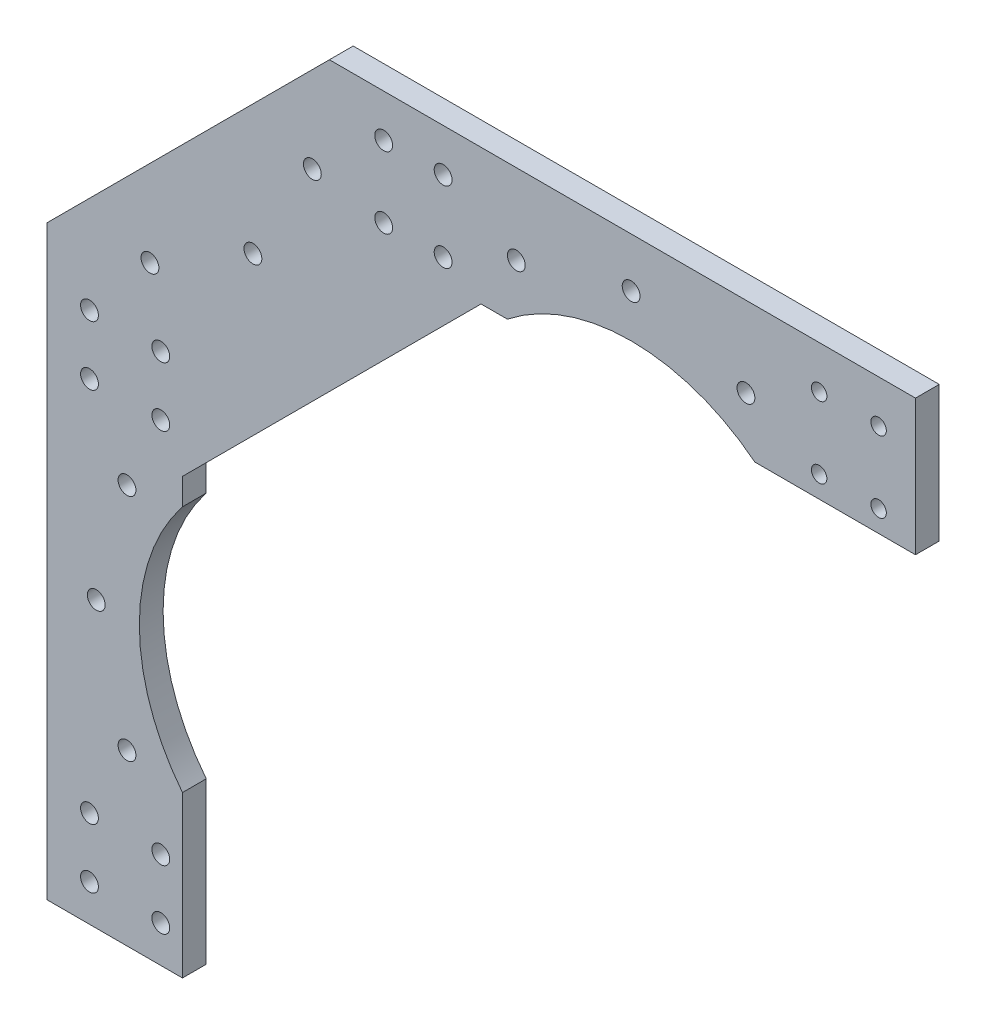
SolidWorks part; units mm, degrees
ref_plane "Front Plane" through (0, 0, 0) normal (0, 0, 1) x (1, 0, 0)
ref_plane "Top Plane" through (0, 0, 0) normal (0, 1, 0) x (1, 0, 0)
ref_plane "Right Plane" through (0, 0, 0) normal (1, 0, 0) x (0, 0, -1)
sketch "Sketch1" plane through (0, 0, 0) normal (0, 0, 1) x (1, 0, 0)
  line L0 (0, 0) -> (0, 75.4924) construction
  line L1 (-98.3263, -47.8405) -> (-75.4924, -47.8405)
  line L2 (-98.3263, -47.8405) -> (-98.3263, 50.769)
  line L4 (-75.4924, -47.8405) -> (-75.4924, 25.2528) construction
  line L5 (-50.769, 98.3263) -> (47.8405, 98.3263)
  line L7 (-25.2528, 75.4924) -> (47.8405, 75.4924) construction
  line L8 (47.8405, 98.3263) -> (47.8405, 75.4924)
  line L9 (0, 0) -> (-75.4924, 0) construction
  line L10 (-25.2528, 75.4924) -> (-75.4924, 25.2528)
  line L11 (-75.4924, 75.4924) -> (-25.2528, 75.4924) construction
  line L12 (-75.4924, 25.2528) -> (-75.4924, 75.4924) construction
  line L13 (-50.769, 98.3263) -> (-98.3263, 50.769)
  line L14 (-98.3263, 98.3263) -> (-50.769, 98.3263) construction
  line L15 (-98.3263, 50.769) -> (-98.3263, 98.3263) construction
  line L16 (-20.8161, 75.4924) -> (-25.2528, 75.4924)
  line L17 (20.8161, 75.4924) -> (47.8405, 75.4924)
  line L18 (-75.4924, 25.2528) -> (-75.4924, 20.8161)
  line L19 (-75.4924, -47.8405) -> (-75.4924, -20.8161)
  line L20 (-75.4924, 20.8161) -> (-75.4924, -20.8161) construction
  line L21 (-20.8161, 75.4924) -> (20.8161, 75.4924) construction
  arc A0 (20.8161, 75.4924) -> (-20.8161, 75.4924) centre (0, 49.2714) ccw
  arc A1 (-75.4924, 20.8161) -> (-75.4924, -20.8161) centre (-49.2714, 0) ccw
  dimension "D1" = 135
extrude "Boss-Extrude1" add sketch "Sketch1" along normal blind 4
ref_axis "Axis1" through (0, 0, -0.2) along (0, 0, 1)
sketch "Sketch3" plane through (0, 0, 4) normal (0, 0, 1) x (1, 0, 0)
  line L0 (-91.1351, 41.6359) -> (-91.1351, 31.6359) construction
  line L1 (-91.1351, -31.6359) -> (-91.1351, -41.6359) construction
  line L2 (-91.1351, -31.6359) -> (-79.1351, -31.6359) construction
  line L3 (-79.1351, -31.6359) -> (-79.1351, -41.6359) construction
  line L4 (-91.1351, -41.6359) -> (-79.1351, -41.6359) construction
  line L5 (-91.1351, 41.6359) -> (-79.1351, 41.6359) construction
  line L6 (-79.1351, 41.6359) -> (-79.1351, 31.6359) construction
  line L7 (-91.1351, 31.6359) -> (-79.1351, 31.6359) construction
  line L8 (31.6359, 91.1351) -> (31.6359, 79.1351) construction
  line L9 (31.6359, 91.1351) -> (41.6359, 91.1351) construction
  line L10 (41.6359, 91.1351) -> (41.6359, 79.1351) construction
  line L11 (31.6359, 79.1351) -> (41.6359, 79.1351) construction
  line L12 (-31.6359, 91.1351) -> (-31.6359, 79.1351) construction
  line L13 (-31.6359, 91.1351) -> (-41.6359, 91.1351) construction
  line L14 (-41.6359, 91.1351) -> (-41.6359, 79.1351) construction
  line L15 (-31.6359, 79.1351) -> (-41.6359, 79.1351) construction
  circle A0 centre (-91.1351, -41.6359) radius 1.5
  circle A1 centre (-91.1351, -31.6359) radius 1.5
  circle A2 centre (-79.1351, -31.6359) radius 1.5
  circle A3 centre (-79.1351, -41.6359) radius 1.5
  circle A4 centre (-91.1351, 31.6359) radius 1.5
  circle A5 centre (-91.1351, 41.6359) radius 1.5
  circle A6 centre (-79.1351, 41.6359) radius 1.5
  circle A7 centre (-79.1351, 31.6359) radius 1.5
  circle A8 centre (31.6359, 79.1351) radius 1.3
  circle A9 centre (31.6359, 91.1351) radius 1.3
  circle A10 centre (41.6359, 91.1351) radius 1.3
  circle A11 centre (41.6359, 79.1351) radius 1.3
  circle A12 centre (-31.6359, 79.1351) radius 1.5
  circle A13 centre (-31.6359, 91.1351) radius 1.5
  circle A14 centre (-41.6359, 91.1351) radius 1.5
  circle A15 centre (-41.6359, 79.1351) radius 1.5
  dimension "D1" = 3
  dimension "D2" = 3
  dimension "D3" = 2.6
  dimension "D4" = 3
extrude "Cut-Extrude1" cut sketch "Sketch3" against normal blind 10
sketch "Sketch4" plane through (0, 0, 4) normal (0, 0, 1) x (1, 0, 0)
  line L0 (0, 0) -> (0, 90) construction
  line L1 (0, 0) -> (-63.6396, 63.6396) construction
  line L2 (0, 0) -> (-90, 0) construction
  line L3 (-84.8236, 19.3185) -> (-90, 0) construction
  line L4 (-90, 0) -> (-84.8236, -19.3185) construction
  line L5 (-80.9601, 53.6396) -> (-63.6396, 63.6396) construction
  line L6 (-63.6396, 63.6396) -> (-69.6582, 69.6582) construction
  line L7 (-19.3185, 84.8236) -> (0, 90) construction
  circle A0 centre (-90, 0) radius 1.5
  circle A1 centre (-63.6396, 63.6396) radius 1.5
  circle A2 centre (0, 90) radius 1.5
  circle A3 centre (-80.9601, 53.6396) radius 1.5
  circle A4 centre (-53.6396, 80.9601) radius 1.5
  circle A5 centre (19.3185, 84.8236) radius 1.5
  circle A6 centre (-19.3185, 84.8236) radius 1.5
  circle A7 centre (-84.8236, 19.3185) radius 1.5
  circle A8 centre (-84.8236, -19.3185) radius 1.5
  dimension "D2" = 3
  dimension "D1" = 45
  dimension "D3" = 90
  dimension "D4" = 75
  dimension "D5" = 20
  dimension "D6" = 90
  dimension "D7" = 75
  dimension "D8" = 75
extrude "Cut-Extrude2" cut sketch "Sketch4" against normal through all
